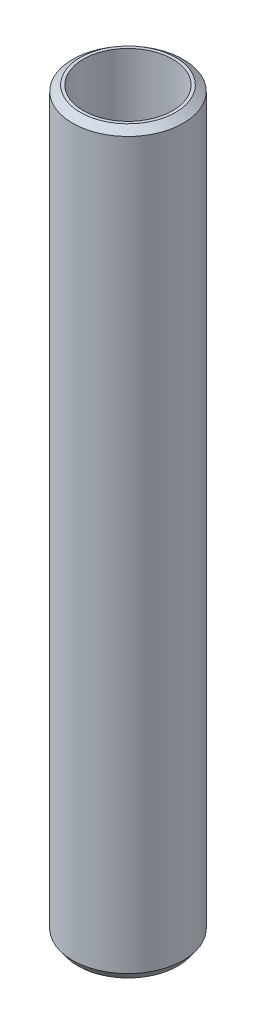
SolidWorks part; units mm, degrees
ref_plane "Front Plane" through (0, 0, 0) normal (0, 0, 1) x (1, 0, 0)
ref_plane "Top Plane" through (0, 0, 0) normal (0, 1, 0) x (1, 0, 0)
ref_plane "Right Plane" through (0, 0, 0) normal (1, 0, 0) x (0, 0, -1)
sketch "Sketch1" plane through (0, 0, 0) normal (0, 1, 0) x (1, 0, 0)
  circle A0 centre (0, 0) radius 45
  dimension "SHAFT_OD" = 90
extrude "Boss-Extrude1" add sketch "Sketch1" along normal blind 600
sketch "Sketch2" plane through (0, 0, 0) normal (0, 1, 0) x (1, 0, 0)
  circle A0 centre (0, 0) radius 36.3208
  dimension "BORE_D" = 72.6416
extrude "Cut-Extrude1" cut sketch "Sketch2" along normal through all
chamfer "Chamfer1" distance 4.4867 angle 54.397 2 edges at (0, 600, 45) (0, 0, 45) first distance on face at (0, 600, 45) first distance on face at (0, 0, 36.3208)
